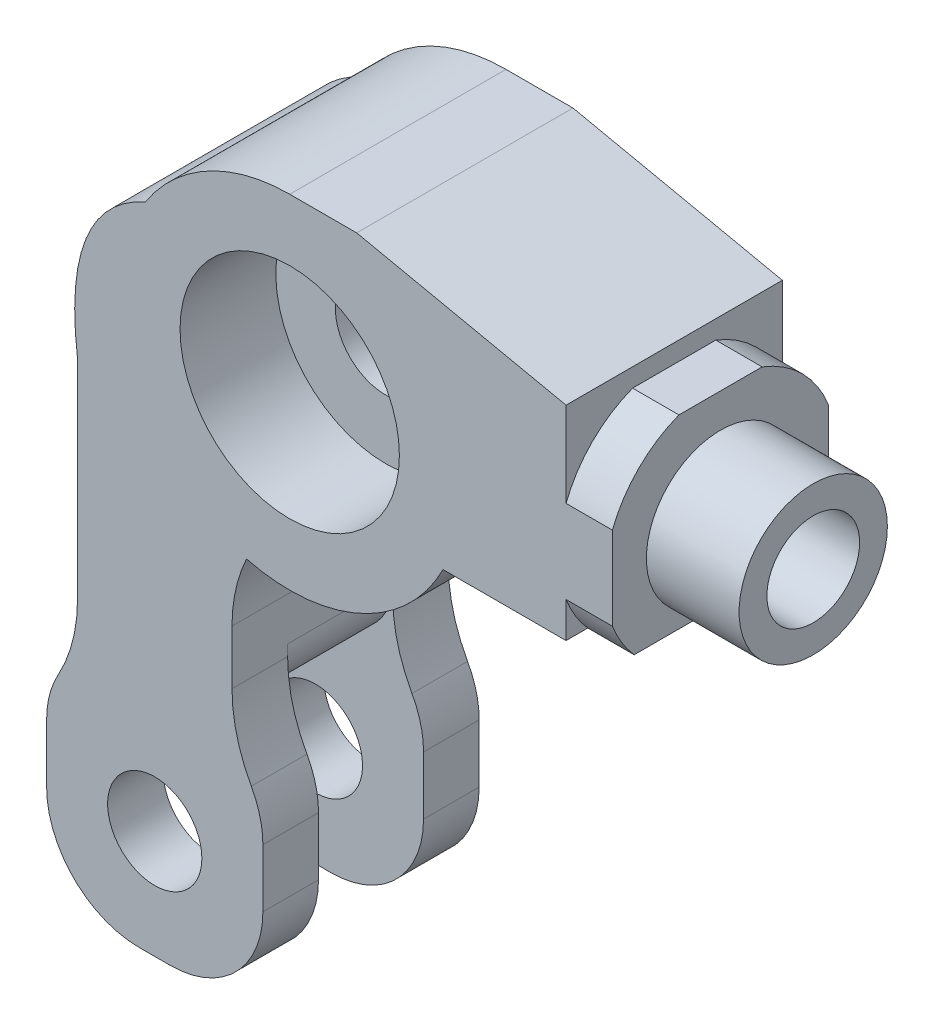
SolidWorks part; units mm, degrees
other "Markup1"
sketch "Sketch6" plane through (2.7225, -1.7628, 7) normal (0.1422, -0.1117, 0.9835) x (0.9563, 0.2719, -0.1074)
ref_plane "Front Plane" through (0, 0, 0) normal (0, 0, 1) x (1, 0, 0)
ref_plane "Top Plane" through (0, 0, 0) normal (0, 1, 0) x (1, 0, 0)
ref_plane "Right Plane" through (0, 0, 0) normal (1, 0, 0) x (0, 0, -1)
sketch "Sketch1" plane through (0, 0, 0) normal (0, 0, 1) x (1, 0, 0)
  line L0 (2.7225, 17.7472) -> (-15.5901, 17.7472)
  line L1 (-15.5901, 17.7472) -> (-15.5901, -1.7628)
  line L2 (-15.5901, -1.7628) -> (-10.5901, -1.7628)
  line L3 (-10.5901, -1.7628) -> (-10.5901, 9.8045)
  line L4 (-10.5901, 12.7472) -> (2.7225, 12.7472)
  line L5 (2.7225, 12.7472) -> (2.7225, 17.7472)
  line L6 (-10.5901, 9.8045) -> (-10.5901, 12.7472)
  line L7 (-13.0901, 0.7496) -> (-1.6827, 0.7496) construction
  line L8 (-13.0901, 0.7496) -> (-8.7219, 15.2372) construction
  circle A2 centre (-8.7219, 15.2372) radius 1.625
  circle A3 centre (-13.0901, 0.7496) radius 1.525
  point P10 (-15.5901, 17.7472)
  dimension "D3" = 3.25
  dimension "D4" = 5
  dimension "D5" = 11.4445
  dimension "D6" = 18.3127
  dimension "D7" = 3.05
  dimension "D11" = 5
  dimension "D2" = 19.51
  dimension "D8" = 2.49
  dimension "D9" = 2.5123
  dimension "D10" = 2.5
extrude "Boss-Extrude1" add sketch "Sketch1" along normal blind 7
sketch "Sketch2" plane through (2.7225, 0, 0) normal (1, 0, 0) x (0, 0, -1)
  line L0 (-7, 12.7472) -> (0, 12.7472) construction
  line L1 (0, 12.7472) -> (0, 17.7472) construction
  circle A0 centre (-3.5, 15.2472) radius 1.5
  dimension "D1" = 3
  dimension "D2" = 2.5
  dimension "D3" = 3.5
extrude "Cut-Extrude1" cut sketch "Sketch2" against normal blind 3
sketch "Sketch3" plane through (0, -1.7628, 0) normal (0, -1, 0) x (1, 0, 0)
  line L0 (-19.2822, 5.2) -> (-8.6938, 5.2)
  line L1 (-15.5901, 7) -> (-10.5901, 7) construction
  line L3 (-8.6938, 5.2) -> (-8.6938, 1.8)
  line L4 (-8.6938, 1.8) -> (-19.2822, 1.8)
  line L5 (-19.2822, 1.8) -> (-19.2822, 5.2)
  line L11 (-19.2822, 5.2) -> (-8.6938, 1.8) construction
  point P6 (-13.988, 3.5)
  dimension "D1" = 3.5
  dimension "D2" = 3.4
extrude "Cut-Extrude2" cut sketch "Sketch3" against normal blind 6.11
fillet "Fillet1" radius 5 2 edges at (-15.5901, 17.7472, 3.5) (-10.5901, 12.7472, 3.5)
sketch "Sketch5" plane through (0, 0, 7) normal (0, 0, 1) x (1, 0, 0)
  line L0 (2.7225, 17.7472) -> (-10.5901, 17.7472)
  line L1 (2.7225, 17.7472) -> (2.7225, 18.7472)
  line L3 (2.7225, 18.7472) -> (-10.5901, 18.7472)
  line L4 (-15.5901, 12.7472) -> (-10.5901, 17.7472)
  spline S0 degree 2 poles (-10.5901, 18.7472) (-16.362, 18.7437) (-15.5901, 12.7472) knots 0 0 0 1 1 1
  dimension "D1" = 1
extrude "Boss-Extrude2" add sketch "Sketch5" against normal up to surface (7 mm away) up to face at (-8.1458, 10.0036, 0)
sketch "Sketch7" plane through (0, 0, 7) normal (0, 0, 1) x (1, 0, 0)
  line L0 (-10.5901, -1.7628) -> (-10.5901, 2.9922)
  line L2 (-10.5901, 2.9922) -> (-9.5901, 2.9922)
  line L3 (-9.5901, -1.7628) -> (-9.5901, 2.9922)
  line L4 (-10.5901, -1.7628) -> (-10.5901, 7.7472) construction
  line L5 (-15.5901, -1.7628) -> (-15.5901, 2.9922)
  line L7 (-15.5901, 2.9922) -> (-16.5901, 2.9922)
  line L8 (-16.5901, -1.7628) -> (-16.5901, 2.9922)
  line L9 (-15.5901, 12.7472) -> (-15.5901, -1.7628) construction
  line L10 (-15.5901, -1.7628) -> (-10.5901, -1.7628)
  line L11 (-16.5901, -1.7628) -> (-16.5901, -2.7628)
  line L12 (-9.5901, -1.7628) -> (-9.5901, -2.7628)
  line L13 (-16.5901, -2.7628) -> (-9.5901, -2.7628)
  dimension "D1" = 1
  dimension "D2" = 1
  dimension "D3" = 1
extrude "Boss-Extrude3" add sketch "Sketch7" against normal up to surface (1.8 mm away) up to face at (-11.5651, 0.7496, 5.2)
extrude "Boss-Extrude4" add sketch "Sketch7<2>" along normal up to surface (-5.2 mm away) from surface up to face at (-14.6151, 0.7496, 1.8) starting at face at (-8.3289, 9.7492, 0)
sketch "Sketch7<2>" plane through (0, 0, 7) normal (0, 0, 1) x (1, 0, 0) same geometry as "Sketch7"
fillet "Fillet4" radius 5 2 edges at (-15.5901, 2.9922, 0.9) (-10.5901, 2.9922, 0.9)
fillet "Fillet5" radius 3 8 edges at (-16.5901, 2.9922, 0.9) (-16.5901, 2.9922, 6.1) (-9.5901, 2.9922, 0.9) (-9.5901, 2.9922, 6.1) (-16.5901, -2.7628, 0.9) (-16.5901, -2.7628, 6.1) (-9.5901, -2.7628, 0.9) (-9.5901, -2.7628, 6.1)
fillet "Fillet6" radius 2 2 edges at (-15.8685, 4.3472, 3.5) (-10.3118, 4.3472, 3.5)
sketch "Sketch8" plane through (2.7225, 0, 0) normal (1, 0, 0) x (0, 0, -1)
  line L7 (-6.35, 11.1176) -> (-0.65, 11.1176)
  line L8 (-6.35, 11.1176) -> (-6.35, 19.3769)
  line L9 (-6.35, 19.3769) -> (-0.65, 19.3769)
  line L10 (-0.65, 11.1176) -> (-0.65, 19.3769)
  line L11 (-6.35, 11.1176) -> (-0.65, 19.3769) construction
  line L12 (-6.35, 19.3769) -> (-0.65, 11.1176) construction
  point P0 (-3.5, 15.2472)
  dimension "D2" = 5.7
extrude "Cut-Extrude3" cut sketch "Sketch8" against normal blind 2.6 from offset 3 offset against normal yes
fillet "Fillet7" radius 0.7 2 edges at (-1.5775, 12.7472, 6.35) (-1.5775, 12.7472, 0.65)
sketch "Sketch9" plane through (2.7225, 0, 0) normal (1, 0, 0) x (0, 0, -1)
  circle A0 centre (-3.5, 15.2472) radius 3.75
  circle A1 centre (-3.5, 15.2472) radius 5.3264
  dimension "D1" = 7.5
extrude "Cut-Extrude5" cut sketch "Sketch9" against normal blind 2.5
sketch "Sketch10" plane through (2.7225, 0, 0) normal (1, 0, 0) x (0, 0, -1)
  circle A0 centre (-3.5, 15.2472) radius 2.4
  circle A1 centre (-3.5, 15.2472) radius 4.87
  dimension "D1" = 4.8
extrude "Cut-Extrude6" cut sketch "Sketch10" against normal blind 1
sketch "Sketch11" plane through (2.7225, 0, 0) normal (1, 0, 0) x (0, 0, -1)
  circle A0 centre (-3.5, 15.2472) radius 1.5
  circle A1 centre (-3.5, 15.2472) radius 2.4
extrude "Boss-Extrude5" add sketch "Sketch11" along normal blind 2
sketch "Sketch12" plane through (0, 0, 7) normal (0, 0, 1) x (1, 0, 0)
  circle A0 centre (-8.7219, 15.2372) radius 3.575
  dimension "D1" = 7.15
extrude "Cut-Extrude7" cut sketch "Sketch12" along normal blind 3.1 from surface starting at face at (-11.5651, 0.7496, 0)
sketch "Sketch14" plane through (0, 0, 7) normal (0, 0, 1) x (1, 0, 0)
  circle A0 centre (-8.7219, 15.2372) radius 3.575
  dimension "D1" = 7.15
extrude "Cut-Extrude8" cut sketch "Sketch14" against normal blind 3.1
sketch "Sketch15" plane through (0, 0, 7) normal (0, 0, 1) x (1, 0, 0)
  circle A0 centre (-8.7219, 15.2372) radius 3.55
  circle A1 centre (-8.7219, 15.2372) radius 5.55
  dimension "D1" = 2
extrude "Boss-Extrude6" add sketch "Sketch15" against normal blind 7
sketch "Sketch16" plane through (0, 0, 3.9) normal (0, 0, 1) x (1, 0, 0)
  circle A0 centre (-7.4738, 12.119) radius 1.4071
extrude "Boss-Extrude7" add sketch "Sketch16" against normal blind 1
sketch "Sketch17" plane through (-2.8775, 0, 0) normal (1, 0, 0) x (0, 0, -1)
  circle A0 centre (-3.5, 15.2472) radius 1.5
extrude "Cut-Extrude9" cut sketch "Sketch17" against normal blind 2.2
sketch "Sketch18" plane through (0, 0, 7) normal (0, 0, 1) x (1, 0, 0)
  line L2 (-4.6976, 18.7472) -> (0.2225, 18.7472)
  line L3 (-8.7219, 20.7872) -> (-6.5553, 20.7872)
  line L4 (-8.7219, 20.7872) -> (-4.6976, 18.7472)
  line L6 (0.2225, 18.7472) -> (0.2225, 19.3472)
  line L7 (0.2225, 19.3472) -> (-6.5553, 20.7872)
  arc A0 (-4.4228, 18.7472) -> (-13.3892, 18.2404) centre (-8.7219, 15.2372) ccw construction
  dimension "D1" = 0.6
extrude "Boss-Extrude8" add sketch "Sketch18" against normal up to surface (7 mm away) up to face at (-7.3687, 9.1943, 0)
sketch "Sketch19" plane through (0, 0, 0) normal (0, 0, -1) x (-1, 0, 0)
  circle A0 centre (8.7219, 15.2372) radius 3.55
extrude "Cut-Extrude10" cut sketch "Sketch19" against normal up to surface (3.1 mm away) up to face at (-7.0969, 15.2372, 3.1)
